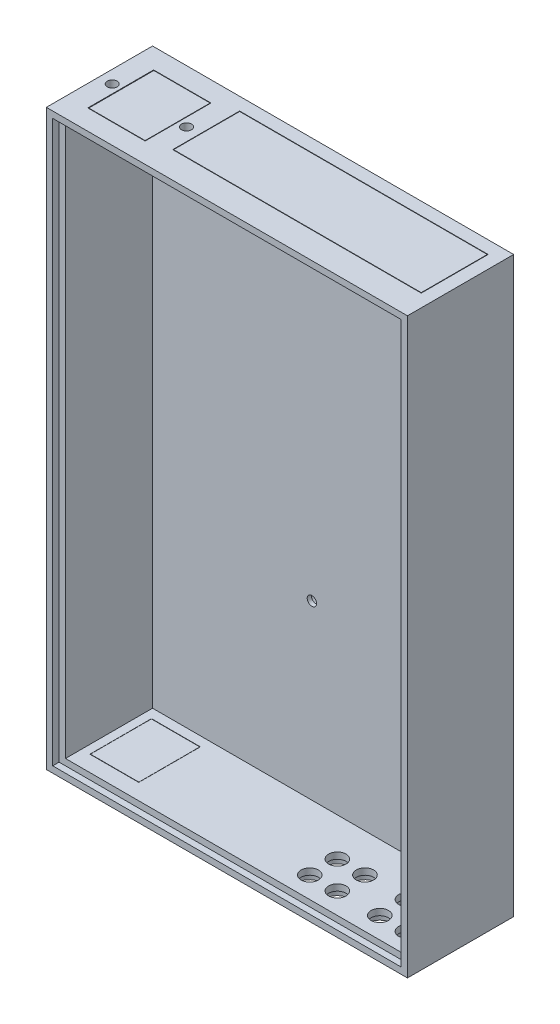
SolidWorks part; units mm, degrees
ref_plane "Front Plane" through (0, 0, 0) normal (0, 0, 1) x (1, 0, 0)
ref_plane "Top Plane" through (0, 0, 0) normal (0, 1, 0) x (1, 0, 0)
ref_plane "Right Plane" through (0, 0, 0) normal (1, 0, 0) x (0, 0, -1)
sketch "Sketch1" plane through (0, 0, 0) normal (0, 0, 1) x (1, 0, 0)
  line L1 (-42.4109, 60.2306) -> (127.5891, 60.2306)
  line L2 (-42.4109, 60.2306) -> (-42.4109, -209.7694)
  line L3 (-42.4109, -209.7694) -> (127.5891, -209.7694)
  line L4 (127.5891, 60.2306) -> (127.5891, -209.7694)
  dimension "D1" = 170
  dimension "D2" = 270
extrude "Boss-Extrude1" add sketch "Sketch1" along normal blind 50
sketch "Sketch2" plane through (0, 0, 50) normal (0, 0, 1) x (1, 0, 0)
  line L0 (-42.4109, 60.2306) -> (-42.4109, -209.7694) construction
  line L1 (-36.4109, 54.2306) -> (121.5891, 54.2306)
  line L2 (-36.4109, 54.2306) -> (-36.4109, -203.7694)
  line L3 (-36.4109, -203.7694) -> (121.5891, -203.7694)
  line L4 (121.5891, 54.2306) -> (121.5891, -203.7694)
  line L5 (127.5891, -209.7694) -> (127.5891, 60.2306) construction
  line L6 (-42.4109, -209.7694) -> (127.5891, -209.7694) construction
  line L7 (127.5891, 60.2306) -> (-42.4109, 60.2306) construction
  dimension "D1" = 6
  dimension "D2" = 6
  dimension "D3" = 6
  dimension "D4" = 6
extrude "Cut-Extrude1" cut sketch "Sketch2" against normal blind 44
sketch "Sketch3" plane through (0, -209.7694, 0) normal (0, -1, 0) x (1, 0, 0)
  line L0 (-42.4109, 50) -> (-42.4109, 0) construction
  line L1 (-32.4109, 39.5) -> (-9.4109, 39.5)
  line L2 (-32.4109, 39.5) -> (-32.4109, 10.5)
  line L3 (-32.4109, 10.5) -> (-9.4109, 10.5)
  line L4 (-9.4109, 39.5) -> (-9.4109, 10.5)
  line L5 (-42.4109, 0) -> (127.5891, 0) construction
  dimension "D1" = 23
  dimension "D2" = 29
  dimension "D3" = 10
  dimension "D4" = 10.5
extrude "Cut-Extrude2" cut sketch "Sketch3" against normal blind 6
sketch "Sketch4" plane through (0, -209.7694, 0) normal (0, -1, 0) x (1, 0, 0)
  line L0 (-9.4109, 39.5) -> (-32.4109, 39.5) construction
  line L1 (-34.9109, 42.5) -> (-6.9109, 42.5)
  line L2 (-34.9109, 42.5) -> (-34.9109, 7.5)
  line L3 (-34.9109, 7.5) -> (-6.9109, 7.5)
  line L4 (-6.9109, 42.5) -> (-6.9109, 7.5)
  line L5 (-32.4109, 10.5) -> (-9.4109, 10.5) construction
  line L6 (-32.4109, 39.5) -> (-32.4109, 10.5) construction
  line L7 (-9.4109, 10.5) -> (-9.4109, 39.5) construction
  dimension "D1" = 3
  dimension "D2" = 3
  dimension "D3" = 2.5
  dimension "D4" = 2.5
extrude "Cut-Extrude3" cut sketch "Sketch4" against normal blind 4.5
chamfer "Chamfer1" distance 5 angle 45 1 edges at (-20.9109, -209.7694, 42.5)
chamfer "Chamfer2" distance 5 angle 45 1 edges at (-20.9109, -209.7694, 7.5)
sketch "Sketch5" plane through (0, -205.2694, 0) normal (0, -1, 0) x (1, 0, 0)
  line L0 (-32.4109, 10.5) -> (-32.4109, 39.5) construction
  line L1 (-32.3109, 39.35) -> (-9.5109, 39.35)
  line L2 (-32.3109, 39.35) -> (-32.3109, 10.65)
  line L3 (-32.3109, 10.65) -> (-9.5109, 10.65)
  line L4 (-9.5109, 39.35) -> (-9.5109, 10.65)
  line L5 (-9.4109, 39.5) -> (-9.4109, 10.5) construction
  line L6 (-9.4109, 10.5) -> (-32.4109, 10.5) construction
  line L7 (-32.4109, 39.5) -> (-9.4109, 39.5) construction
  dimension "D1" = 0.1
  dimension "D2" = 0.1
  dimension "D3" = 0.15
  dimension "D4" = 0.15
extrude "Boss-Extrude2" add sketch "Sketch5" against normal blind 1.5 separate body
sketch "Sketch6" plane through (0, -81.1347, -81.1347) normal (0, -0.7071, -0.7071) x (1, 0, 0)
  text T0 "I" font "Century Gothic" height in points 18
extrude "Cut-Extrude4" cut sketch "Sketch6" against normal blind 0.25
sketch "Sketch7" plane through (0, -106.1347, 106.1347) normal (0, -0.7071, 0.7071) x (1, 0, 0)
  text T0 "0" font "Century Gothic" height in points 15
extrude "Cut-Extrude5" cut sketch "Sketch7" against normal blind 0.25
sketch "Sketch8" plane through (0, -209.7694, 0) normal (0, -1, 0) x (1, 0, 0)
  text T0 "12V PS" font "Century Gothic" height in points 20
extrude "Cut-Extrude6" cut sketch "Sketch8" against normal blind 0.25
sketch "Sketch9" plane through (0, 54.2306, 0) normal (0, -1, 0) x (1, 0, 0)
  line L1 (121.5891, 6) -> (4.5891, 6)
  line L2 (121.5891, 6) -> (121.5891, 37.5)
  line L3 (121.5891, 37.5) -> (4.5891, 37.5)
  line L4 (4.5891, 6) -> (4.5891, 37.5)
  dimension "D1" = 31.5
  dimension "D2" = 117
extrude "Cut-Extrude7" cut sketch "Sketch9" against normal blind 6
sketch "Sketch10" plane through (0, 60.2306, 0) normal (0, 1, 0) x (1, 0, 0)
  line L0 (127.5891, -50) -> (-42.4109, -50) construction
  line L1 (-5.4109, -40.5) -> (-32.4109, -40.5)
  line L2 (-5.4109, -40.5) -> (-5.4109, -9.5)
  line L3 (-5.4109, -9.5) -> (-32.4109, -9.5)
  line L4 (-32.4109, -40.5) -> (-32.4109, -9.5)
  line L8 (-42.4109, -50) -> (-42.4109, 0) construction
  dimension "D1" = 27
  dimension "D2" = 31
  dimension "D3" = 9.5
  dimension "D4" = 10
extrude "Cut-Extrude8" cut sketch "Sketch10" against normal blind 6
sketch "Sketch11" plane through (0, 60.2306, 0) normal (0, 1, 0) x (1, 0, 0)
  line L0 (-5.4109, -40.5) -> (-5.4109, -9.5) construction
  line L1 (-32.4109, -40.5) -> (-5.4109, -40.5) construction
  circle A0 centre (-1.4109, -25) radius 2.35
  dimension "D1" = 4.7
  dimension "D2" = 4
  dimension "D3" = 15.5
extrude "Cut-Extrude9" cut sketch "Sketch11" against normal blind 6
sketch "Sketch12" plane through (0, 60.2306, 0) normal (0, 1, 0) x (1, 0, 0)
  line L0 (-32.4109, -9.5) -> (-32.4109, -40.5) construction
  line L1 (-32.4109, -40.5) -> (-5.4109, -40.5) construction
  circle A0 centre (-36.4109, -25) radius 2.35
  dimension "D1" = 4.7
  dimension "D2" = 4
  dimension "D3" = 15.5
extrude "Cut-Extrude10" cut sketch "Sketch12" against normal blind 6
sketch "Sketch13" plane through (0, 60.2306, 0) normal (0, 1, 0) x (1, 0, 0)
  line L0 (4.5891, -37.5) -> (4.5891, -6) construction
  line L1 (4.7891, -6.2) -> (121.3891, -6.2)
  line L2 (4.7891, -6.2) -> (4.7891, -37.3)
  line L3 (4.7891, -37.3) -> (121.3891, -37.3)
  line L4 (121.3891, -6.2) -> (121.3891, -37.3)
  line L5 (-36.4109, -6) -> (121.5891, -6) construction
  line L6 (121.5891, -6) -> (121.5891, -50) construction
  line L7 (121.5891, -37.5) -> (4.5891, -37.5) construction
  dimension "D1" = 0.2
  dimension "D2" = 0.2
  dimension "D3" = 0.2
  dimension "D4" = 0.2
extrude "Boss-Extrude3" add sketch "Sketch13" against normal blind 6 separate body
sketch "Sketch14" plane through (0, 60.2306, 0) normal (0, 1, 0) x (1, 0, 0)
  line L0 (-32.3109, -39.35) -> (-32.3109, -10.65) construction
  line L1 (-5.6109, -40.3) -> (-32.1109, -40.3)
  line L2 (-5.6109, -40.3) -> (-5.6109, -9.7)
  line L3 (-5.6109, -9.7) -> (-32.1109, -9.7)
  line L4 (-32.1109, -40.3) -> (-32.1109, -9.7)
  line L5 (-5.4109, -40.5) -> (-5.4109, -9.5) construction
  line L6 (-5.4109, -9.5) -> (-32.4109, -9.5) construction
  line L7 (-32.4109, -40.5) -> (-5.4109, -40.5) construction
  dimension "D1" = 0.2
  dimension "D2" = 0.2
  dimension "D3" = 0.2
  dimension "D4" = 0.2
extrude "Boss-Extrude4" add sketch "Sketch14" against normal blind 6 separate body
sketch "Sketch15" plane through (0, -209.7694, 0) normal (0, -1, 0) x (1, 0, 0)
  line L0 (-42.4109, 50) -> (127.5891, 50) construction
  line L1 (127.5891, 50) -> (127.5891, 0) construction
  circle A0 centre (114.5891, 37) radius 4.1
  circle A1 centre (101.5891, 37) radius 4.1
  circle A2 centre (81.5891, 37) radius 4.1
  circle A3 centre (68.5891, 37) radius 4.1
  circle A4 centre (114.5891, 24) radius 4.1
  circle A5 centre (101.5891, 24) radius 4.1
  circle A6 centre (81.5891, 24) radius 4.1
  circle A7 centre (68.5891, 24) radius 4.1
  dimension "D1" = 8.2
  dimension "D2" = 8.2
  dimension "D3" = 8.2
  dimension "D4" = 8.2
  dimension "D5" = 8.2
  dimension "D6" = 8.2
  dimension "D7" = 8.2
  dimension "D8" = 8.2
  dimension "D9" = 13
  dimension "D10" = 13
  dimension "D11" = 13
  dimension "D12" = 13
  dimension "D13" = 13
  dimension "D14" = 13
  dimension "D15" = 13
  dimension "D16" = 13
  dimension "D17" = 13
  dimension "D18" = 13
  dimension "D19" = 13
  dimension "D20" = 20
  dimension "D21" = 13
extrude "Cut-Extrude11" cut sketch "Sketch15" against normal blind 6
sketch "Sketch16" plane through (0, -209.7694, 0) normal (0, -1, 0) x (1, 0, 0)
  circle A0 centre (114.5891, 37) radius 5.75
  circle A1 centre (114.5891, 24) radius 5.75
  circle A2 centre (101.5891, 37) radius 5.75
  circle A3 centre (101.5891, 24) radius 5.75
  circle A4 centre (81.5891, 37) radius 5.75
  circle A5 centre (68.5891, 37) radius 5.75
  circle A6 centre (81.5891, 24) radius 5.75
  circle A7 centre (68.5891, 24) radius 5.75
  dimension "D1" = 11.5
  dimension "D2" = 11.5
  dimension "D3" = 11.5
  dimension "D4" = 11.5
  dimension "D5" = 11.5
  dimension "D6" = 11.5
  dimension "D7" = 11.5
  dimension "D8" = 11.5
extrude "Cut-Extrude12" cut sketch "Sketch16" against normal blind 3
sketch "Sketch17" plane through (0, -209.7694, 0) normal (0, -1, 0) x (1, 0, 0)
  text T0 "+" font "Century Gothic" height in points 25
extrude "Cut-Extrude13" cut sketch "Sketch17" against normal blind 0.25
sketch "Sketch18" plane through (0, -209.7694, 0) normal (0, -1, 0) x (1, 0, 0)
  text T0 "-" font "Century Gothic" height in points 25
extrude "Cut-Extrude14" cut sketch "Sketch18" against normal blind 0.25
sketch "Sketch19" plane through (0, 0, 6) normal (0, 0, 1) x (1, 0, 0)
  line L0 (121.5891, -203.7694) -> (121.5891, 60.2306) construction
  line L1 (4.5891, 60.2306) -> (121.5891, 60.2306) construction
  circle A0 centre (88.5891, 27.4806) radius 2.2
  circle A1 centre (38.5891, 27.4806) radius 2.2
  circle A2 centre (88.5891, -122.5194) radius 2.2
  circle A3 centre (38.5891, -122.5194) radius 2.2
  dimension "D9" = 4.4
  dimension "D10" = 4.4
  dimension "D11" = 4.4
  dimension "D12" = 4.4
  dimension "D1" = 33
  dimension "D2" = 32.75
  dimension "D3" = 33
  dimension "D4" = 50
  dimension "D5" = 32.75
  dimension "D6" = 150
  dimension "D7" = 50
  dimension "D8" = 150
extrude "Cut-Extrude15" cut sketch "Sketch19" against normal blind 10
sketch "Sketch20" plane through (0, 0, 0) normal (0, 0, -1) x (-1, 0, 0)
  circle A0 centre (-88.5891, 27.4806) radius 3.75
  circle A1 centre (-38.5891, 27.4806) radius 3.75
  circle A2 centre (-38.5891, -122.5194) radius 3.75
  circle A3 centre (-88.5891, -122.5194) radius 3.75
  dimension "D1" = 7.5
  dimension "D2" = 7.5
  dimension "D3" = 7.5
  dimension "D4" = 7.5
extrude "Cut-Extrude16" cut sketch "Sketch20" against normal blind 4
sketch "Sketch21" plane through (0, 0, 50) normal (0, 0, 1) x (1, 0, 0)
  line L0 (121.5891, 54.2306) -> (-36.4109, 54.2306) construction
  line L1 (-39.4109, 57.2306) -> (124.5891, 57.2306)
  line L2 (-39.4109, 57.2306) -> (-39.4109, -206.7694)
  line L3 (-39.4109, -206.7694) -> (124.5891, -206.7694)
  line L4 (124.5891, 57.2306) -> (124.5891, -206.7694)
  line L5 (-36.4109, 54.2306) -> (-36.4109, -203.7694) construction
  line L6 (121.5891, -203.7694) -> (121.5891, 54.2306) construction
  line L7 (-36.4109, -203.7694) -> (121.5891, -203.7694) construction
  dimension "D1" = 3
  dimension "D2" = 3
  dimension "D3" = 3
  dimension "D4" = 3
extrude "Cut-Extrude17" cut sketch "Sketch21" against normal blind 3
